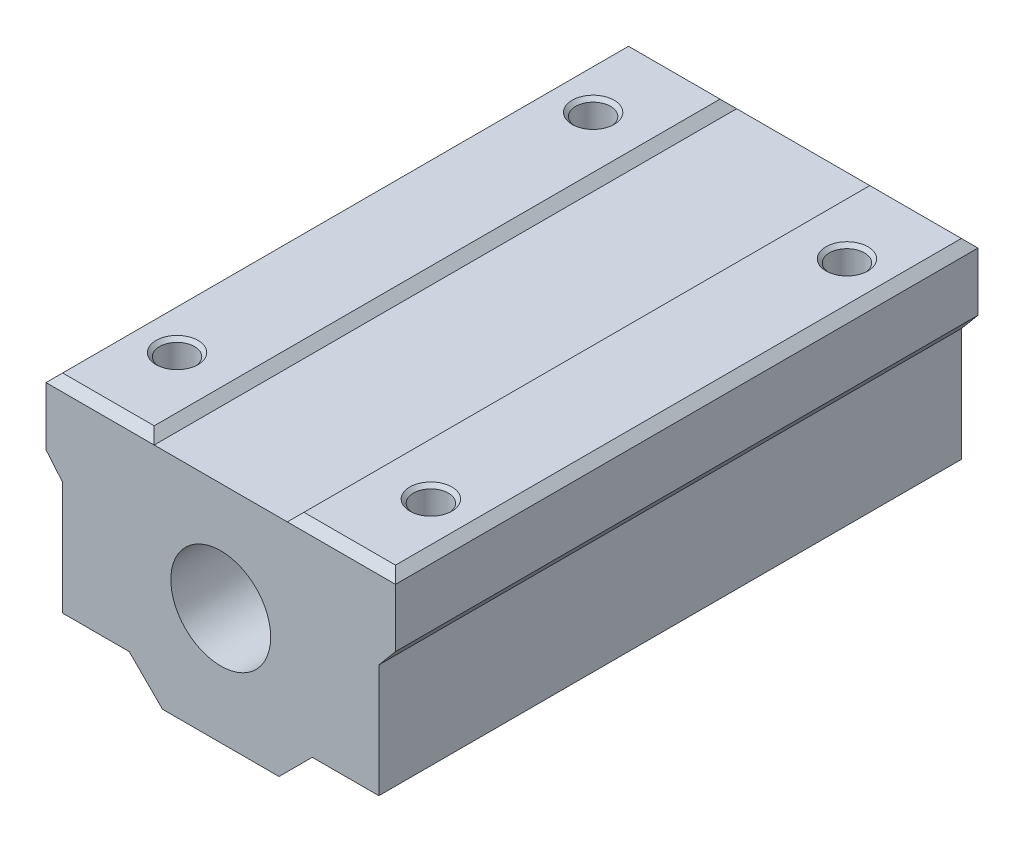
SolidWorks part; units mm, degrees
ref_plane "Plano frontal" through (0, 0, 0) normal (0, 0, 1) x (1, 0, 0)
ref_plane "Plano superior" through (0, 0, 0) normal (0, 1, 0) x (1, 0, 0)
ref_plane "Plano direito" through (0, 0, 0) normal (1, 0, 0) x (0, 0, -1)
sketch "Esboço1" plane through (0, 0, 0) normal (0, 0, 1) x (1, 0, 0)
  line L0 (0, 14) -> (0, -14) construction
  line L1 (8, 13) -> (-8, 13)
  line L2 (21, 14) -> (21, 6)
  line L3 (21, 6) -> (19, 3.6165)
  line L4 (19, 3.6165) -> (19, -10)
  line L5 (19, -10) -> (11, -10)
  line L6 (11, -10) -> (7, -14)
  line L7 (7, -14) -> (-7, -14)
  line L8 (8, 13) -> (8, 14)
  line L9 (8, 14) -> (21, 14)
  line L10 (-8, 14) -> (-21, 14)
  line L11 (-8, 13) -> (-8, 14)
  line L12 (-11, -10) -> (-7, -14)
  line L13 (-19, -10) -> (-11, -10)
  line L14 (-19, 3.6165) -> (-19, -10)
  line L15 (-21, 6) -> (-19, 3.6165)
  line L16 (-21, 14) -> (-21, 6)
  circle A0 centre (0, 0) radius 6
  point P21 (0, 13)
  dimension "D11" = 12
  dimension "D1" = 21
  dimension "D2" = 13
  dimension "D3" = 8
  dimension "D4" = 28
  dimension "D5" = 7
  dimension "D6" = 135
  dimension "D7" = 1
  dimension "D8" = 220
  dimension "D9" = 24
  dimension "D10" = 19
extrude "Ressalto-extrusão1" add sketch "Esboço1" against normal blind 70
chamfer "Chanfro1" distance 1 angle 45 8 edges at (14.5, 14, -70) (21, 14, -35) (14.5, 14, 0) (8, 14, -35) (-14.5, 14, -70) (-21, 14, -35) (-14.5, 14, 0) (-8, 14, -35)
hole_wizard "Furo roscado de M51" positions "Esboço2" profile "Esboço3" tap size "M5" standard "DIN" end condition through all
sketch "Esboço2" plane through (0, 14, 0) normal (0, 1, 0) x (1, 0, 0)
  line L0 (-21, 0) -> (-21, 70) construction
  line L1 (-8, 0) -> (-21, 0) construction
  point P0 (15.25, 10)
  point P2 (15.25, 60)
  point P4 (-15.25, 60)
  point P6 (-15.25, 10)
  dimension "D1" = 30.5
  dimension "D2" = 5.75
  dimension "D3" = 50
  dimension "D4" = 10
sketch "Esboço3" plane through (15.25, 14, -10) normal (1, 0, 0) x (0, 0, 1)
  line L0 (0, 0) -> (0, 28)
  line L1 (0, 28) -> (2.1, 28)
  line L2 (2.1, 28) -> (2.1, 0.425)
  line L3 (2.1, 0.425) -> (2.525, 0)
  line L5 (2.525, 0) -> (0, 0)
  line L6 (-2.1, 0.425) -> (-2.525, 0) construction
  line L11 (0, -6.35) -> (0, 107.95) construction
  dimension "Thru Tap Drill Dia." = 4.2
  dimension "Thru Tap Drill Depth" = 28
  dimension "Near C'Sink Dia." = 5.05
  dimension "Near C'Sink Angle" = 90
cosmetic thread "Rosca de furo1" parameters "D1"=12, "D2"=5
cosmetic thread "Rosca de furo2" parameters "D1"=12, "D2"=5
cosmetic thread "Rosca de furo3" parameters "D1"=12, "D2"=5
cosmetic thread "Rosca de furo4" parameters "D1"=12, "D2"=5
chamfer "Chanfro2" distance 1 angle 45 4 edges at (17.35, -10, -60) (-15.25, -10, -62.1) (-15.25, -10, -12.1) (17.35, -10, -10)
